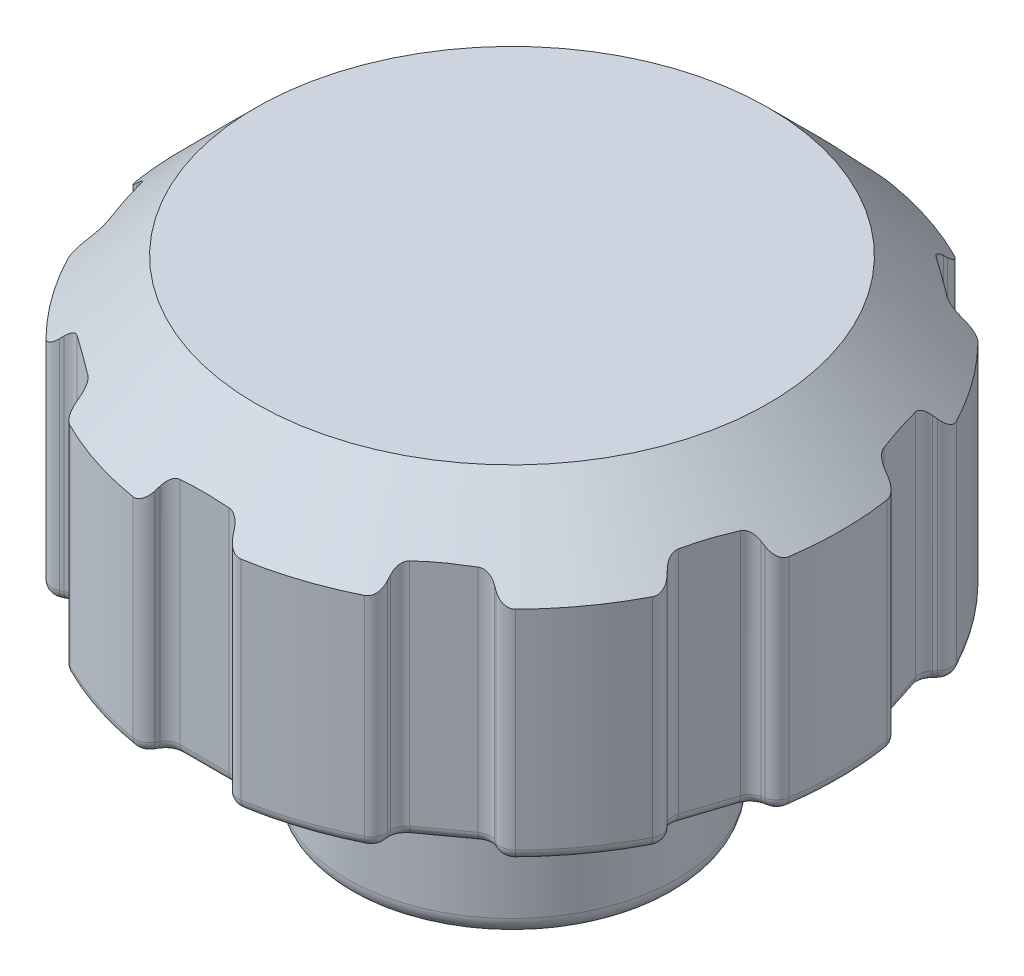
SolidWorks part; units mm, degrees
ref_plane "Ebene vorne" through (0, 0, 0) normal (0, 0, 1) x (1, 0, 0)
ref_plane "Ebene oben" through (0, 0, 0) normal (0, 1, 0) x (1, 0, 0)
ref_plane "Ebene rechts" through (0, 0, 0) normal (1, 0, 0) x (0, 0, -1)
ref_axis "Achse1" through (0, -4.6, 0) along (0, 1, 0)
sketch "Skizze1" plane through (0, 0, 0) normal (0, 1, 0) x (1, 0, 0)
  circle A0 centre (0, 0) radius 9
  dimension "D1" = 18
extrude "Aufsatz-Linear austragen1" add sketch "Skizze1" along normal blind 8
sketch "Skizze2" plane through (0, 0, 0) normal (0, -1, 0) x (1, 0, 0)
  circle A1 centre (0, 0) radius 4.5
  dimension "D1" = 9
extrude "Aufsatz-Linear austragen2" add sketch "Skizze2" along normal blind 5
sketch "Skizze3" plane through (0, -5, 0) normal (0, -1, 0) x (1, 0, 0)
  line L0 (1.3, -2.7037) -> (1.3, 2.7037)
  line L1 (0, 0) -> (1.3, 0) construction
  line L2 (0, 0) -> (-3, 0) construction
  circle A0 centre (0, 0) radius 3
  dimension "D2" = 6
  dimension "D1" = 4.3
extrude "Schnitt-Linear austragen2" cut sketch "Skizze3" against normal blind 6.5 contours L0 A0 region at (-0.6076, -5, 0)
fillet "Verrundung1" radius 2 1 edges at (0, 8, 9) profile chamfer
sketch "Skizze4" plane through (0, 8, 0) normal (0, 1, 0) x (1, 0, 0)
  line L0 (1.2, 8.9196) -> (0.9, 8.4)
  line L1 (0.9, 8.4) -> (-0.9, 8.4)
  line L2 (-0.9, 8.4) -> (-1.2, 8.9196)
  line L3 (0, 0) -> (0, 8.4) construction
  line L6 (0, 8.4) -> (0, 9) construction
  circle A0 centre (0, 0) radius 9 construction
  dimension "D1" = 60
  dimension "D2" = 2.4
  dimension "D3" = 0.6
extrude "Schnitt-Linear austragen3" cut sketch "Skizze4" against normal through all flip side to cut
pattern_circular "Kreismuster1" count 10 over 360 about axis through (0, -4.6, 0) along (0, 1, 0) of "Schnitt-Linear austragen3"
fillet "Verrundung2" radius 0.4 40 edges at (-1.2, 3, -8.9196) (-0.9, 3.276, -8.4) (1.2, 3, -8.9196) (0.9, 3.276, -8.4) (4.2093, 3.276, -7.3247) (4.272, 3, -7.9215) (-4.272, 3, -7.9215) (-4.2093, 3.276, -7.3247) (-5.6655, 3.276, -6.2667) (-6.2137, 3, -6.5108) (-8.1123, 3, -3.8976) (-7.7108, 3.276, -3.4517) (-8.267, 3.276, -1.7398) (-8.8539, 3, -1.6151) (-8.8539, 3, 1.6151) (-8.267, 3.276, 1.7398) (-7.7108, 3.276, 3.4517) (-8.1123, 3, 3.8976) (-6.2137, 3, 6.5108) (-5.6655, 3.276, 6.2667) (-4.2093, 3.276, 7.3247) (-4.272, 3, 7.9215) (-1.2, 3, 8.9196) (-0.9, 3.276, 8.4) (0.9, 3.276, 8.4) (1.2, 3, 8.9196) (4.272, 3, 7.9215) (4.2093, 3.276, 7.3247) (5.6655, 3.276, 6.2667) (6.2137, 3, 6.5108) (8.1123, 3, 3.8976) (7.7108, 3.276, 3.4517) (8.267, 3.276, 1.7398) (8.8539, 3, 1.6151) (8.8539, 3, -1.6151) (8.267, 3.276, -1.7398) (7.7108, 3.276, -3.4517) (8.1123, 3, -3.8976) (6.2137, 3, -6.5108) (5.6655, 3.276, -6.2667)
fillet "Verrundung3" radius 0.3 81 edges at (1.2393, 0, -8.8453) (1.0396, 0, -8.6418) (0.869, 0, -8.4536) (0, 0, -8.4) (-0.869, 0, -8.4536) (-1.0396, 0, -8.6418) (-1.2393, 0, -8.8453) (-2.7812, 0, -8.5595) (-4.1965, 0, -7.8844) (-4.2385, 0, -7.6024) (-4.2658, 0, -7.3499) (-4.9374, 0, -6.7957) (-5.672, 0, -6.3283) (-5.9206, 0, -6.3803) (-6.2018, 0, -6.4275) (-7.2812, 0, -5.2901) (-8.0294, 0, -3.912) (-7.8976, 0, -3.6592) (-7.7713, 0, -3.4388) (-7.9889, 0, -2.5957) (-8.3084, 0, -1.7858) (-8.5401, 0, -1.6818) (-8.7953, 0, -1.5547) (-9, 0, 0) (-8.7953, 0, 1.5547) (-8.5401, 0, 1.6818) (-8.3084, 0, 1.7858) (-7.9889, 0, 2.5957) (-7.7713, 0, 3.4388) (-7.8976, 0, 3.6592) (-8.0294, 0, 3.912) (-7.2812, 0, 5.2901) (-6.2018, 0, 6.4275) (-5.9206, 0, 6.3803) (-5.672, 0, 6.3283) (-4.9374, 0, 6.7957) (-4.2658, 0, 7.3499) (-4.2385, 0, 7.6024) (-4.1965, 0, 7.8844) (-2.7812, 0, 8.5595) (-1.2393, 0, 8.8453) (-1.0396, 0, 8.6418) (-0.869, 0, 8.4536) (0, 0, 8.4) (0.869, 0, 8.4536) (1.0396, 0, 8.6418) (1.2393, 0, 8.8453) (2.7812, 0, 8.5595) (4.1965, 0, 7.8844) (4.2385, 0, 7.6024) (4.2658, 0, 7.3499) (4.9374, 0, 6.7957) (5.672, 0, 6.3283) (5.9206, 0, 6.3803) (6.2018, 0, 6.4275) (7.2812, 0, 5.2901) (8.0294, 0, 3.912) (7.8976, 0, 3.6592) (7.7713, 0, 3.4388) (7.9889, 0, 2.5957) (8.3084, 0, 1.7858) (8.5401, 0, 1.6818) (8.7953, 0, 1.5547) (9, 0, 0) (8.7953, 0, -1.5547) (8.5401, 0, -1.6818) (8.3084, 0, -1.7858) (7.9889, 0, -2.5957) (7.7713, 0, -3.4388) (7.8976, 0, -3.6592) (8.0294, 0, -3.912) (7.2812, 0, -5.2901) (6.2018, 0, -6.4275) (5.9206, 0, -6.3803) (5.672, 0, -6.3283) (4.9374, 0, -6.7957) (4.2658, 0, -7.3499) (4.2385, 0, -7.6024) (4.1965, 0, -7.8844) (2.7812, 0, -8.5595) (0, 0, -4.5)
fillet "Verrundung4" radius 0.5 1 edges at (0, -5, -4.5)
chamfer "Fase1" distance 0.7 angle 45 2 edges at (1.3, -5, 0) (-3, -5, 0)
